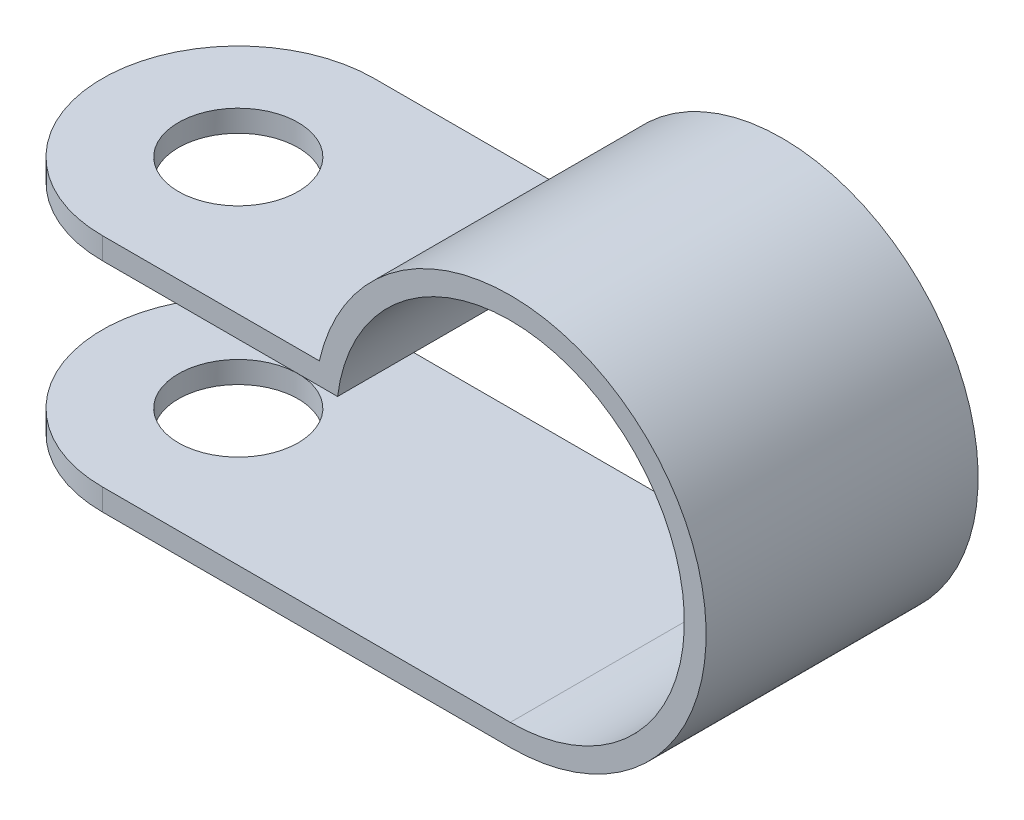
SolidWorks part; units mm, degrees
ref_plane "Front Plane" through (0, 0, 0) normal (0, 0, 1) x (1, 0, 0)
ref_plane "Top Plane" through (0, 0, 0) normal (0, 1, 0) x (1, 0, 0)
ref_plane "Right Plane" through (0, 0, 0) normal (1, 0, 0) x (0, 0, -1)
sketch "Sketch1" plane through (0, 0, 0) normal (0, 0, 1) x (1, 0, 0)
  line L0 (0, 8.382) -> (12.3635, 8.382)
  line L1 (19.05, 0) -> (0, 0)
  line L2 (0, 0) -> (0, 0.762)
  line L3 (0, 0.762) -> (19.05, 0.762)
  line L4 (0, 8.382) -> (0, 7.62)
  line L5 (0, 7.62) -> (13.0018, 7.62)
  arc A0 (12.3635, 8.382) -> (19.05, 0) centre (19.05, 6.858) cw
  arc A1 (13.0018, 7.62) -> (19.05, 0.762) centre (19.05, 6.858) cw
  dimension "D3" = 6.858
  dimension "D1" = 0.762
  dimension "D2" = 0.762
  dimension "D4" = 6.858
  dimension "D5" = 19.05
extrude "Boss-Extrude1" add sketch "Sketch1" along normal blind 9.525
sketch "Sketch2" plane through (0, 8.382, 0) normal (0, 1, 0) x (1, 0, 0)
  line L0 (12.3635, -9.525) -> (0, -9.525) construction
  line L1 (12.3635, 0) -> (0, 0) construction
  line L2 (0, -9.525) -> (0, 0) construction
  line L3 (4.7625, -9.525) -> (0, -9.525)
  line L4 (0, -9.525) -> (0, 0)
  line L5 (0, 0) -> (4.7625, 0)
  arc A0 (4.7625, -9.525) -> (4.7625, 0) centre (4.7625, -4.7625) cw
  circle A1 centre (4.7625, -4.7625) radius 2.0955
  line M1 (12.3635, 0) -> (0, 0)
  line M2 (0, 0) -> (0, -9.525)
  line M3 (0, -9.525) -> (12.3635, -9.525)
  dimension "D1" = 4.191
extrude "Cut-Extrude1" cut sketch "Sketch2" against normal through all contours A1 | A0 M2 M1 | A0 L4 M3 region at (1.0638, 8.382, 1.0638) region at (1.0638, 8.382, 8.4612) region at (4.7625, 8.382, 4.7625)
ref_plane "Plane1" through (0, 0, 4.7625) normal (0, 0, -1) x (-1, 0, 0)
ref_plane "Plane2" through (12.3635, 0, 0) normal (1, 0, 0) x (0, 0, -1)
ref_axis "Axis1" through (19.05, 6.858, 32.2614) along (0, 0, -1)
ref_plane "Plane3" through (19.05, 0, 0) normal (1, 0, 0) x (0, 0, -1)
equation "\"D2@Sketch1\"=\"D1@Sketch1\""
equation "\"D3@Sketch1\"=0.54in/2"
